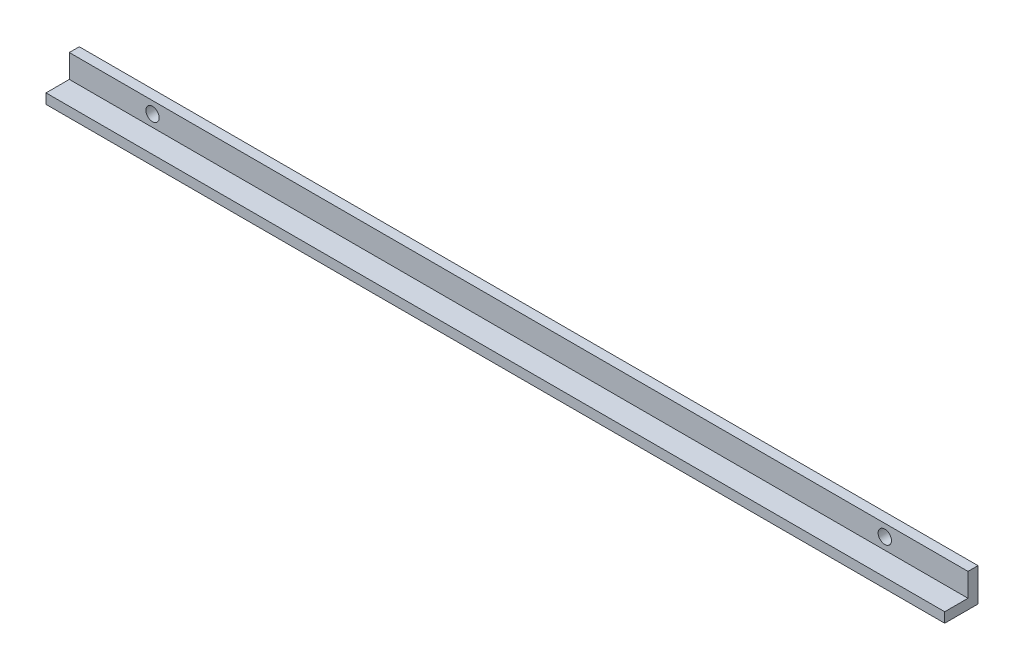
SolidWorks part; units mm, degrees
ref_plane "Спереди" through (0, 0, 0) normal (0, 0, 1) x (1, 0, 0)
ref_plane "Сверху" through (0, 0, 0) normal (0, 1, 0) x (1, 0, 0)
ref_plane "Справа" through (0, 0, 0) normal (1, 0, 0) x (0, 0, -1)
sketch "Эскиз1" plane through (0, 0, 0) normal (1, 0, 0) x (0, 0, -1)
  line L0 (0, 0) -> (-10, 0)
  line L1 (-10, 0) -> (-10, 3)
  line L2 (-10, 3) -> (-3, 3)
  line L3 (-3, 10) -> (-3, 3)
  line L6 (-3, 10) -> (0, 10)
  line L7 (0, 10) -> (0, 0)
  dimension "D1" = 3
  dimension "D2" = 10
extrude "Бобышка-Вытянуть1" add sketch "Эскиз1" along normal blind 270
sketch "Эскиз2" plane through (0, 0, 3) normal (0, 0, 1) x (1, 0, 0)
  line L0 (135, 10) -> (135, 3) construction
  line L1 (270, 10) -> (0, 10) construction
  line L2 (270, 3) -> (0, 3) construction
  line L3 (0, 10) -> (0, 3) construction
  circle A0 centre (25, 6.5) radius 2
  circle A1 centre (245, 6.5) radius 2
  dimension "D1" = 4
  dimension "D2" = 25
extrude "Вырез-Вытянуть1" cut sketch "Эскиз2" against normal through all
